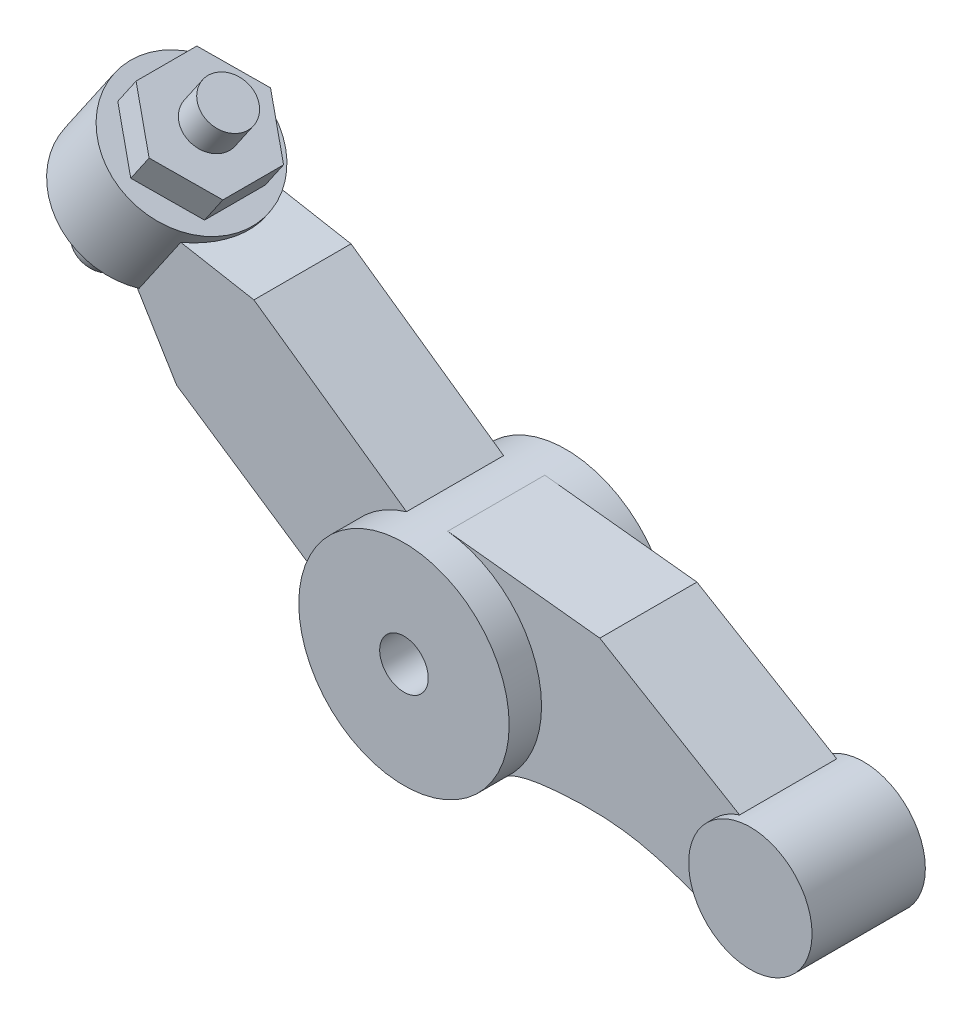
SolidWorks part; units mm, degrees
ref_plane "Front Plane" through (0, 0, 0) normal (0, 0, 1) x (1, 0, 0)
ref_plane "Top Plane" through (0, 0, 0) normal (0, 1, 0) x (1, 0, 0)
ref_plane "Right Plane" through (0, 0, 0) normal (1, 0, 0) x (0, 0, -1)
sketch "Sketch1" plane through (0, 0, 0) normal (0, 0, 1) x (1, 0, 0)
  line L0 (-1.9282, 0) -> (3.8439, 0) construction
  line L1 (0, 2.6251) -> (0, 0) construction
  line L2 (0, 0) -> (-3.6604, 2.5129) construction
  line L3 (3.7473, 0.0599) -> (2.02, 1.0881)
  line L4 (2.02, 1.0881) -> (0.1405, 1.2924)
  line L5 (-3.4694, 2.7912) -> (-3.8515, 2.2347)
  line L6 (-3.4694, 2.7912) -> (-2.2542, 2.5705)
  line L7 (-2.2542, 2.5705) -> (-0.3688, 1.2466)
  line L8 (-3.8515, 2.2347) -> (-3.2088, 1.1799)
  line L9 (-3.2088, 1.1799) -> (-1.2958, -0.1038)
  circle A0 centre (0, 0) radius 1.3
  circle A1 centre (0, 0) radius 0.3
  circle A2 centre (3.98, -0.6662) radius 0.7625
  spline S0 degree 3 poles (3.3744, -1.1295) (2.7785, -0.9066) (2.407, -0.786) (1.502, -0.8075) (0.9965, -0.8554) (0.8565, -0.9779) knots 0 0 0 0 0.647248 0.71824 1 1 1 1
  point P21 (-1.569, 2.3374)
  point P22 (-2.2542, 2.5705)
  dimension "D1" = 2.6
  dimension "D2" = 0.6
  dimension "D3" = 1.525
  dimension "D4" = 0.68
  dimension "D5" = 3.98
  dimension "D6" = 4.44
  dimension "D7" = 0.675
  dimension "D8" = 0.819
  dimension "D9" = 34.47
extrude "Boss-Extrude1" add sketch "Sketch1" along normal mid plane 2 contours A0 A1 region at (0.9403, 0.8436, 0)
extrude "Boss-Extrude2" add sketch "Sketch1<3>" along normal mid plane 1.4 separate body contours A2 region at (3.98, -0.6662, 0)
sketch "Sketch1<3>" plane through (0, 0, 0) normal (0, 0, 1) x (1, 0, 0) same geometry as "Sketch1"
extrude "Boss-Extrude3" add sketch "Sketch1<4>" along normal mid plane 1.2 contours S0 A2 L3 L4 A0 region at (2.1564, 0.0671, 0)
sketch "Sketch1<4>" plane through (0, 0, 0) normal (0, 0, 1) x (1, 0, 0) same geometry as "Sketch1"
extrude "Boss-Extrude4" add sketch "Sketch1<5>" along normal mid plane 1.2 contours A0 L7 L6 L5 L8 L9 region at (-2.2138, 1.5198, 0)
sketch "Sketch1<5>" plane through (0, 0, 0) normal (0, 0, 1) x (1, 0, 0) same geometry as "Sketch1"
sketch "Sketch2" plane through (0, 0, 0) normal (0, 0, 1) x (1, 0, 0)
  line L0 (-3.8515, 2.2347) -> (-3.3572, 2.9547)
  line L1 (-3.3572, 2.9547) -> (-3.6828, 3.1782)
  line L2 (-3.6828, 3.1782) -> (-4.8331, 1.5026)
  line L3 (-4.321, 1.9457) -> (-3.8515, 2.2347)
  line L4 (-3.4694, 2.7912) -> (-3.8515, 2.2347) construction
  arc A0 (-4.8331, 1.5026) -> (-4.321, 1.9457) centre (-4.6351, 1.7912) ccw
  point P9 (-4.3332, 1.9683)
  point P10 (-4.3335, 1.9689)
  point P12 (-4.321, 1.9457)
  dimension "D3" = 0.35
  dimension "D1" = 0.72
  dimension "D2" = 0.395
  dimension "D4" = 1
revolve "Revolve1" add sketch "Sketch2" angle 360 about L2
sketch "Sketch3" plane through (0, 0, 0) normal (0, 0, 1) x (1, 0, 0)
  line L0 (-3.6253, 3.262) -> (-4.2366, 2.3716)
  line L1 (-4.2366, 2.3716) -> (-4.9868, 2.8866)
  line L2 (-4.9868, 2.8866) -> (-4.3756, 3.777)
  line L3 (-4.3756, 3.777) -> (-3.6253, 3.262)
  line L5 (-4.5027, 2.6818) -> (-3.8515, 2.2347) construction
  line L6 (-3.3572, 2.9547) -> (-4.0085, 3.4018) construction
  point P3 (-4.1771, 2.4582)
  point P5 (-3.6828, 3.1782)
  dimension "D1" = 1.08
  dimension "D2" = 0.91
revolve "Revolve2" add sketch "Sketch3" angle 360 about L0
sketch "Sketch4" plane through (0.3607, 0.5255, 0) normal (0.566, 0.8244, 0) x (0.8244, -0.566, 0)
  line L1 (-4.835, -0.7506) -> (-4.185, -0.3753)
  line L2 (-4.185, -0.3753) -> (-4.185, 0.3753)
  line L3 (-4.185, 0.3753) -> (-4.835, 0.7506)
  line L4 (-4.835, 0.7506) -> (-5.485, 0.3753)
  line L5 (-5.485, 0.3753) -> (-5.485, -0.3753)
  line L6 (-5.485, -0.3753) -> (-4.835, -0.7506)
  circle A0 centre (-4.835, 0) radius 0.65 construction
  dimension "D1" = 1.3
extrude "Boss-Extrude5" add sketch "Sketch4" along normal blind 0.4
sketch "Sketch5" plane through (0.5871, 0.8552, 0) normal (0.566, 0.8244, 0) x (0.8244, -0.566, 0)
  circle A0 centre (-4.835, 0) radius 0.3
  dimension "D1" = 0.6
extrude "Boss-Extrude6" add sketch "Sketch5" along normal blind 0.4
